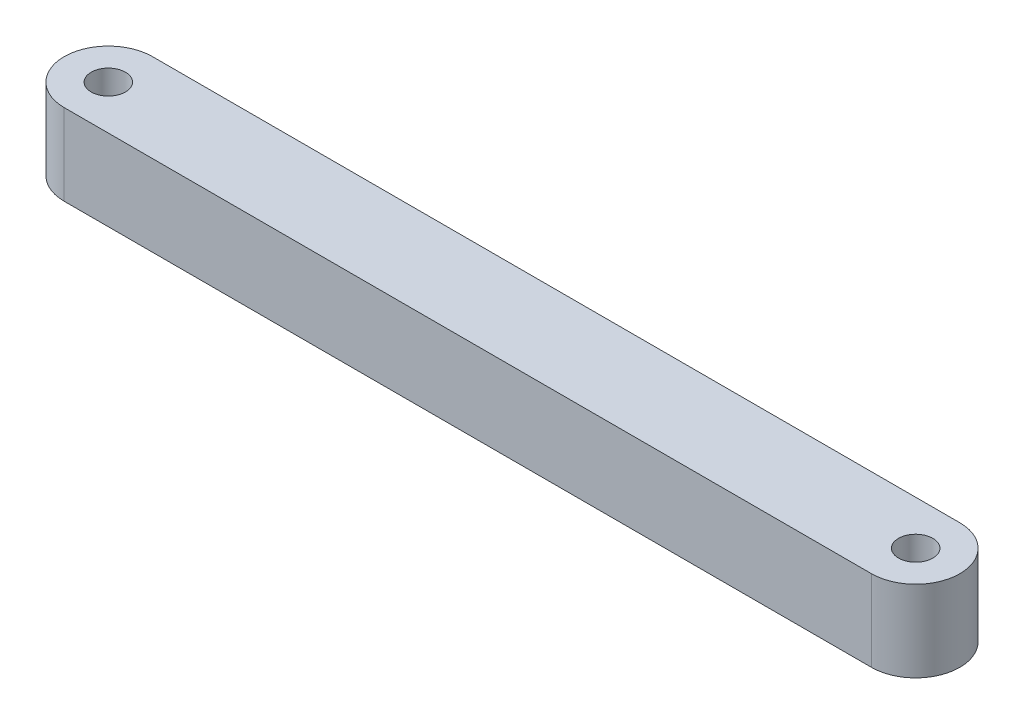
SolidWorks part; units mm, degrees
ref_plane "Front Plane" through (0, 0, 0) normal (0, 0, 1) x (1, 0, 0)
ref_plane "Top Plane" through (0, 0, 0) normal (0, 1, 0) x (1, 0, 0)
ref_plane "Right Plane" through (0, 0, 0) normal (1, 0, 0) x (0, 0, -1)
sketch "Sketch1" plane through (0, 0, 0) normal (0, 1, 0) x (1, 0, 0)
  line L0 (0, 0) -> (101.6, 0) construction
  line L1 (0, 5.5563) -> (101.6, 5.5563)
  line L2 (0, -5.5563) -> (101.6, -5.5563)
  arc A1 (0, 5.5563) -> (0, -5.5563) centre (0, 0) ccw
  arc A2 (101.6, -5.5563) -> (101.6, 5.5563) centre (101.6, 0) ccw
  point P3 (50.8, 0)
  dimension "D1" = 11.1125
  dimension "D2" = 101.6
extrude "Boss-Extrude1" add sketch "Sketch1" along normal blind 10.2108
sketch "Sketch2" plane through (0, 10.2108, 0) normal (0, 1, 0) x (1, 0, 0)
  circle A1 centre (101.6, 0) radius 2.159
  circle A2 centre (0, 0) radius 2.159
  point P2 (0, 0)
  dimension "D3" = 4.318
  dimension "D1" = 101.6
extrude "Cut-Extrude1" cut sketch "Sketch2" against normal through all
sketch "Sketch3" plane through (0, 10.2108, 0) normal (0, 1, 0) x (1, 0, 0)
  circle A0 centre (0, 0) radius 4.9721
  dimension "D1" = 9.9441
ref_plane "Plane1" through (0, 5.1054, 0) normal (0, 1, 0) x (1, 0, 0)
